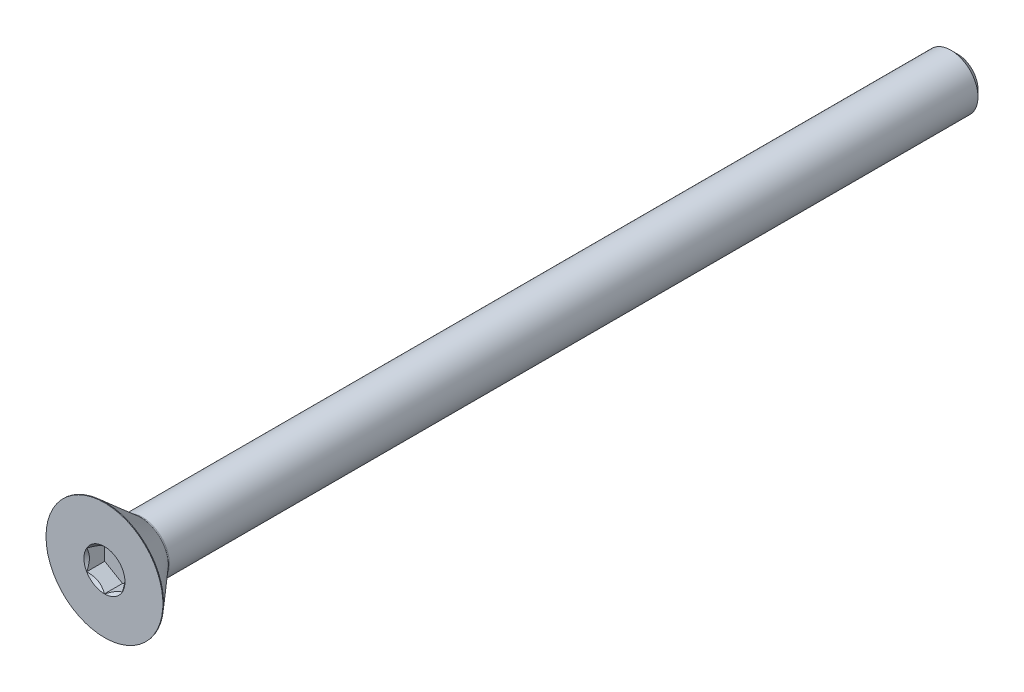
SolidWorks part; units mm, degrees
ref_plane "Front Plane" through (0, 0, 0) normal (0, 0, 1) x (1, 0, 0)
ref_plane "Top Plane" through (0, 0, 0) normal (0, 1, 0) x (1, 0, 0)
ref_plane "Right Plane" through (0, 0, 0) normal (1, 0, 0) x (0, 0, -1)
sketch "Sketch1" plane through (0, 0, 0) normal (1, 0, 0) x (0, 0, -1)
  line L0 (-38.1, 0) -> (38.1, 0) construction
  line L1 (-38.1, 0) -> (-38.1, 5.2197)
  line L2 (-38.1, 5.2197) -> (-38.0355, 5.2197)
  line L3 (-38.0355, 5.2197) -> (-34.8742, 2.4716)
  line L4 (-38.0355, -5.2197) -> (-34.8742, -2.4716)
  line L5 (38.1, 0) -> (38.1, 2.413)
  line L6 (38.1, 2.413) -> (-34.8742, 2.413)
  line L7 (37.5047, 2.413) -> (38.1, 1.8177)
  line L8 (38.0504, 2.4989) -> (38.4473, 1.8115) construction
  line L9 (38.4473, 1.8115) -> (38.8441, 2.4989) construction
  line L10 (38.8441, 2.4989) -> (38.0504, 2.4989) construction
  line L11 (38.0752, 2.456) -> (38.8193, 2.456)
  line L12 (38.8193, 2.456) -> (38.4969, 1.8974)
  line L13 (38.4969, 1.8974) -> (38.3977, 1.8974)
  line L14 (38.3977, 1.8974) -> (38.0752, 2.456)
  line L15 (38.4473, 1.8974) -> (38.4473, 1.8115) construction
  line L16 (38.1, 2.413) -> (38.7945, 2.413) construction
  line L17 (38.4473, 2.4989) -> (38.4473, 2.413) construction
  line L18 (38.1, -2.413) -> (-34.8742, -2.413)
  arc A0 (-34.8742, 2.4716) -> (-34.7174, 2.413) centre (-34.7174, 2.6521) ccw
  point P2 (0, 0)
  point P23 (-36.4871, 0)
  point P27 (38.4473, 2.456)
  point P30 (36.9094, -2.413)
  point P31 (-32.1075, 2.413)
  point P32 (35.4901, 2.413)
  point P33 (-34.8742, 5.2197)
  point P34 (-38.0355, -5.2197)
  point P37 (-31.4551, 2.413)
  dimension "Length" = 76.2
  dimension "Head Height" = 3.2258
  dimension "Head Diameter" = 10.4394
  dimension "Countersink Angle" = 82
  dimension "Screw Size Decimal Equivalent" = 4.826
  dimension "Pitch" = 0.7937
  dimension "D4" = 0.0992
  dimension "D3" = 45
  dimension "D5" = 0.5953
  dimension "D6" = 1.6129
  dimension "D1" = 1.1906
  dimension "D7" = 2.6098
  dimension "D8" = 2.6098
  dimension "D9" = 3.2623
  dimension "D2" = 0.0645
sketch "Sketch8" plane through (0, 0, 0) normal (0, 0, 1) x (1, 0, 0)
  line L1 (0, 1.8331) -> (-1.5875, 0.9165)
  line L2 (-1.5875, 0.9165) -> (-1.5875, -0.9165)
  line L3 (-1.5875, -0.9165) -> (0, -1.8331)
  line L4 (0, -1.8331) -> (1.5875, -0.9165)
  line L5 (1.5875, -0.9165) -> (1.5875, 0.9165)
  line L6 (1.5875, 0.9165) -> (0, 1.8331)
  circle A0 centre (0, 0) radius 1.5875 construction
  dimension "Drive Size" = 3.175
sketch "Sketch2" plane through (0, 0, 0) normal (1, 0, 0) x (0, 0, -1)
  line L0 (-38.0355, 5.2197) -> (-34.8742, 2.4716) construction
  line L1 (-38.1, 0) -> (-38.1, 5.2197) construction
  line L2 (-38.0355, 5.2197) -> (-34.8742, 2.4716)
  line L3 (-38.1, 0) -> (-38.1, 5.2197)
  line L4 (-38.1, 5.2197) -> (-38.0355, 5.2197) construction
  line L5 (-38.1, 5.2197) -> (-38.0355, 5.2197)
  line L6 (-34.7174, 2.413) -> (37.5047, 2.413)
  line L7 (37.5047, 2.413) -> (38.1, 1.8177)
  line L8 (38.1, 1.8177) -> (38.1, 0)
  line L9 (38.1, 0) -> (-38.1, 0)
  arc A0 (-34.8742, 2.4716) -> (-34.7174, 2.413) centre (-34.7174, 2.6521) ccw construction
  arc A1 (-34.8742, 2.4716) -> (-34.7174, 2.413) centre (-34.7174, 2.6521) ccw
revolve "Revolve1" add sketch "Sketch2" angle 360 about L9
sketch "Sketch9" plane through (0, 0, 38.1) normal (0, 0, 1) x (1, 0, 0)
  line L0 (1.5875, -0.9165) -> (1.5875, 0.9165) construction
  line L1 (0, -1.8331) -> (1.5875, -0.9165) construction
  line L2 (-1.5875, -0.9165) -> (0, -1.8331) construction
  line L3 (-1.5875, 0.9165) -> (-1.5875, -0.9165) construction
  line L4 (0, 1.8331) -> (-1.5875, 0.9165) construction
  line L5 (1.5875, 0.9165) -> (0, 1.8331) construction
  line L6 (1.5875, -0.9165) -> (1.5875, 0.9165)
  line L7 (0, -1.8331) -> (1.5875, -0.9165)
  line L8 (-1.5875, -0.9165) -> (0, -1.8331)
  line L9 (-1.5875, 0.9165) -> (-1.5875, -0.9165)
  line L10 (0, 1.8331) -> (-1.5875, 0.9165)
  line L11 (1.5875, 0.9165) -> (0, 1.8331)
sketch "Sketch10" plane through (0, 0, 38.1) normal (0, 0, 1) x (1, 0, 0)
  circle A0 centre (0, 0) radius 1.8331
extrude "Cut-Extrude2" cut sketch "Sketch10" against normal up to vertex (1.6129 mm away) draft 45 up to point (0, 0, 36.4871)
extrude "Cut-Extrude1" cut sketch "Sketch9" against normal up to vertex (1.6129 mm away) up to point (0, 0, 36.4871)
ref_plane "Plane1" [suppressed] through (0, 0, 34.7174) normal (0, 0, 1) x (1, 0, 0)
split "Split1" [suppressed] bodies to split 111
sketch "Sketch3" [suppressed] plane through (0, 0, -38.1) normal (0, 0, -1) x (-1, 0, 0)
  circle A0 centre (0, 0) radius 2.413 construction
  circle A1 centre (0, 0) radius 2.413
curve "Helix/Spiral1" [suppressed] pitch 0.7937 height 76.2 turns 96
sketch "Sketch4" [suppressed] plane through (0, 0, 0) normal (1, 0, 0) x (0, 0, -1)
  line L0 (38.0752, 2.456) -> (38.8193, 2.456) construction
  line L1 (38.3977, 1.8974) -> (38.0752, 2.456) construction
  line L2 (38.4969, 1.8974) -> (38.3977, 1.8974) construction
  line L3 (38.8193, 2.456) -> (38.4969, 1.8974) construction
  line L4 (38.0752, 2.456) -> (38.8193, 2.456)
  line L5 (38.3977, 1.8974) -> (38.0752, 2.456)
  line L6 (38.4969, 1.8974) -> (38.3977, 1.8974)
  line L7 (38.8193, 2.456) -> (38.4969, 1.8974)
sweep "Cut-Sweep1" [suppressed] cut profiles "Sketch4" path "Helix/Spiral1"
sketch "Sketch7" [suppressed] plane through (0, 0, 34.7174) normal (0, 0, 1) x (1, 0, 0)
  circle A0 centre (0, 0) radius 2.413
extrude "Boss-Extrude2" [suppressed] add sketch "Sketch7" against normal up to next draft 20
equation "\"D4@Sketch1\" = \"Pitch@Sketch1\" / 8"
equation "\"D5@Sketch1\"=\"Pitch@Sketch1\"*0.75"
equation "\"D4@Helix/Spiral1\"=\"Pitch@Sketch1\""
equation "\"D3@Helix/Spiral1\"=\"Length@Sketch1\""
equation "\"D6@Sketch1\"=\"Head Height@Sketch1\"/2"
equation "\"D1@Sketch1\"=\"Pitch@Sketch1\"*1.5"
equation "\"D7@Sketch1\"=\"Head Diameter@Sketch1\"*0.25"
equation "\"D8@Sketch1\"=\"D7@Sketch1\""
equation "\"D9@Sketch1\"=1.25*\"D7@Sketch1\""
